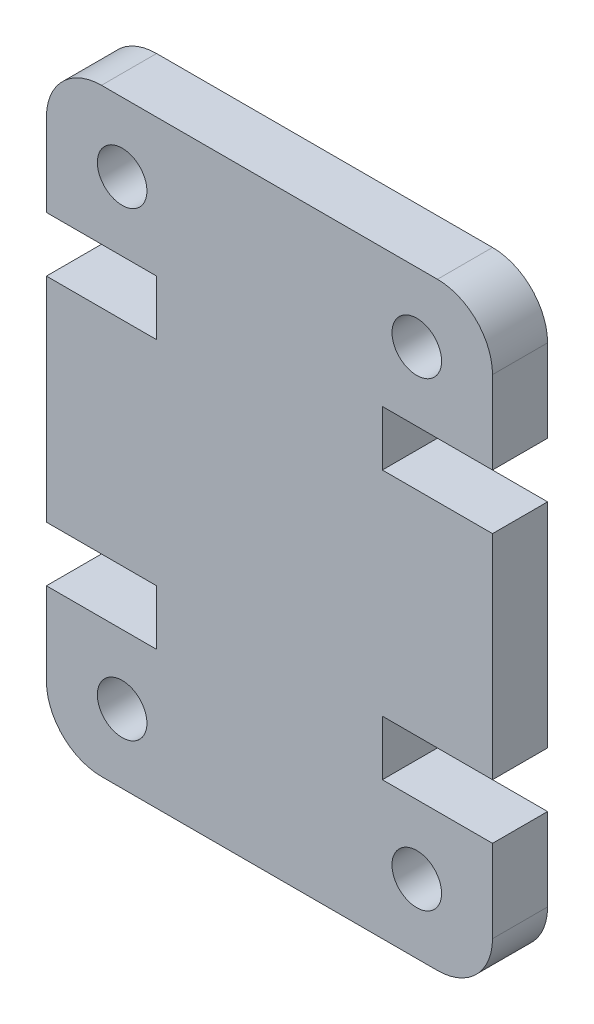
SolidWorks part; units mm, degrees
ref_plane "Front Plane" through (0, 0, 0) normal (0, 0, 1) x (1, 0, 0)
ref_plane "Top Plane" through (0, 0, 0) normal (0, 1, 0) x (1, 0, 0)
ref_plane "Right Plane" through (0, 0, 0) normal (1, 0, 0) x (0, 0, -1)
sketch "Sketch1" plane through (0, 0, 0) normal (0, 0, 1) x (1, 0, 0)
  line L0 (0, 14.74) -> (0, 7)
  line L1 (16.2, 2) -> (16.2, 5)
  line L2 (12.2, 5) -> (16.2, 5)
  line L3 (2, 0) -> (14.2, 0)
  line L4 (16.2, 7) -> (12.2, 7)
  line L5 (12.2, 7) -> (12.2, 5)
  line L6 (16.2, 14.74) -> (16.2, 7)
  line L7 (4, 7) -> (4, 5)
  line L8 (0, 19.74) -> (0, 16.74)
  line L9 (4, 16.74) -> (0, 16.74)
  line L10 (0, 7) -> (4, 7)
  line L11 (0, 14.74) -> (4, 14.74)
  line L12 (4, 5) -> (0, 5)
  line L13 (4, 14.74) -> (4, 16.74)
  line L14 (12.2, 14.74) -> (12.2, 16.74)
  line L15 (16.2, 14.74) -> (12.2, 14.74)
  line L16 (0, 2) -> (0, 5)
  line L17 (2, 21.74) -> (14.2, 21.74)
  line L18 (12.2, 16.74) -> (16.2, 16.74)
  line L19 (16.2, 19.74) -> (16.2, 16.74)
  line L20 (8.1, 21.74) -> (8.1, 0) construction
  line L21 (0, 10.87) -> (16.2, 10.87) construction
  circle A0 centre (13.45, 2.5) radius 0.9
  arc A1 (16.2, 2) -> (14.2, 0) centre (14.2, 2) cw
  circle A2 centre (2.75, 19.24) radius 0.9
  arc A3 (0, 2) -> (2, 0) centre (2, 2) ccw
  arc A4 (0, 19.74) -> (2, 21.74) centre (2, 19.74) cw
  circle A5 centre (2.75, 2.5) radius 0.9
  arc A6 (16.2, 19.74) -> (14.2, 21.74) centre (14.2, 19.74) ccw
  circle A7 centre (13.45, 19.24) radius 0.9
  point P15 (8.1, 10.87)
  dimension "D1" = 1.8
  dimension "D2" = 2
  dimension "D3" = 2.75
  dimension "D4" = 8.1
  dimension "D5" = 2.5
  dimension "D8" = 10.87
  dimension "D6" = 5
extrude "Boss-Extrude1" add sketch "Sketch1" along normal blind 4
sketch "Sketch2" plane through (0, 0, 0) normal (0, 0, -1) x (-1, 0, 0)
  line L0 (0, 0) -> (-16.2, 0)
  line L1 (-16.2, 0) -> (-16.2, 21.74)
  line L2 (-16.2, 21.74) -> (0, 21.74)
  line L3 (0, 21.74) -> (0, 0)
extrude "Cut-Extrude1" cut sketch "Sketch2" against normal blind 2
equation "\"D4@Sketch1\"= \"fingerWidth@parametersSketch@prostheticParameters.SLDPRT\" / 2'PIP width"
equation "\"D8@Sketch1\"= ( \"HL@parametersSketch@prostheticParameters.SLDPRT\" * 0.204 - 4 - 12 ) / 2 'PIP length - Sil. Sht MIP - Sil.Sht PIP"
equation "\"D1@Sketch1\"= 1.5 + \"tol1@parametersSketch@prostheticParameters.SLDPRT\""
